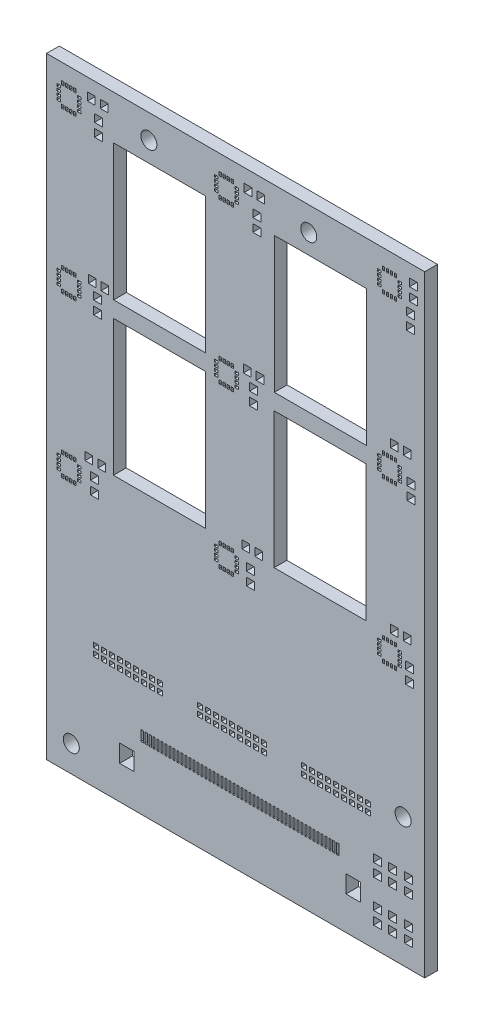
SolidWorks part; units mm, degrees
ref_plane "Plan de face" through (0, 0, 0) normal (0, 0, 1) x (1, 0, 0)
ref_plane "Plan de dessus" through (0, 0, 0) normal (0, 1, 0) x (1, 0, 0)
ref_plane "Plan de droite" through (0, 0, 0) normal (1, 0, 0) x (0, 0, -1)
sketch "Model" plane through (0, 0, 0) normal (0, 0, 1) x (1, 0, 0)
  line L0 (15.68, 10.185) -> (15.68, 10.775)
  line L1 (15.68, 10.775) -> (16.32, 10.775)
  line L2 (16.32, 10.775) -> (16.32, 10.185)
  line L3 (16.32, 10.185) -> (15.68, 10.185)
  line L4 (15.68, 9.225) -> (15.68, 9.815)
  line L5 (15.68, 9.815) -> (16.32, 9.815)
  line L6 (16.32, 9.815) -> (16.32, 9.225)
  line L7 (16.32, 9.225) -> (15.68, 9.225)
  line L8 (14.68, 10.185) -> (14.68, 10.775)
  line L9 (14.68, 10.775) -> (15.32, 10.775)
  line L10 (15.32, 10.775) -> (15.32, 10.185)
  line L11 (15.32, 10.185) -> (14.68, 10.185)
  line L12 (14.68, 9.225) -> (14.68, 9.815)
  line L13 (14.68, 9.815) -> (15.32, 9.815)
  line L14 (15.32, 9.815) -> (15.32, 9.225)
  line L15 (15.32, 9.225) -> (14.68, 9.225)
  line L16 (13.68, 10.185) -> (13.68, 10.775)
  line L17 (13.68, 10.775) -> (14.32, 10.775)
  line L18 (14.32, 10.775) -> (14.32, 10.185)
  line L19 (14.32, 10.185) -> (13.68, 10.185)
  line L20 (13.68, 9.225) -> (13.68, 9.815)
  line L21 (13.68, 9.815) -> (14.32, 9.815)
  line L22 (14.32, 9.815) -> (14.32, 9.225)
  line L23 (14.32, 9.225) -> (13.68, 9.225)
  line L24 (12.68, 10.185) -> (12.68, 10.775)
  line L25 (12.68, 10.775) -> (13.32, 10.775)
  line L26 (13.32, 10.775) -> (13.32, 10.185)
  line L27 (13.32, 10.185) -> (12.68, 10.185)
  line L28 (12.68, 9.225) -> (12.68, 9.815)
  line L29 (12.68, 9.815) -> (13.32, 9.815)
  line L30 (13.32, 9.815) -> (13.32, 9.225)
  line L31 (13.32, 9.225) -> (12.68, 9.225)
  line L32 (11.68, 10.185) -> (11.68, 10.775)
  line L33 (11.68, 10.775) -> (12.32, 10.775)
  line L34 (12.32, 10.775) -> (12.32, 10.185)
  line L35 (12.32, 10.185) -> (11.68, 10.185)
  line L36 (11.68, 9.225) -> (11.68, 9.815)
  line L37 (11.68, 9.815) -> (12.32, 9.815)
  line L38 (12.32, 9.815) -> (12.32, 9.225)
  line L39 (12.32, 9.225) -> (11.68, 9.225)
  line L40 (10.68, 10.185) -> (10.68, 10.775)
  line L41 (10.68, 10.775) -> (11.32, 10.775)
  line L42 (11.32, 10.775) -> (11.32, 10.185)
  line L43 (11.32, 10.185) -> (10.68, 10.185)
  line L44 (10.68, 9.225) -> (10.68, 9.815)
  line L45 (10.68, 9.815) -> (11.32, 9.815)
  line L46 (11.32, 9.815) -> (11.32, 9.225)
  line L47 (11.32, 9.225) -> (10.68, 9.225)
  line L48 (9.68, 10.185) -> (9.68, 10.775)
  line L49 (9.68, 10.775) -> (10.32, 10.775)
  line L50 (10.32, 10.775) -> (10.32, 10.185)
  line L51 (10.32, 10.185) -> (9.68, 10.185)
  line L52 (9.68, 9.225) -> (9.68, 9.815)
  line L53 (9.68, 9.815) -> (10.32, 9.815)
  line L54 (10.32, 9.815) -> (10.32, 9.225)
  line L55 (10.32, 9.225) -> (9.68, 9.225)
  line L56 (8.68, 10.185) -> (8.68, 10.775)
  line L57 (8.68, 10.775) -> (9.32, 10.775)
  line L58 (9.32, 10.775) -> (9.32, 10.185)
  line L59 (9.32, 10.185) -> (8.68, 10.185)
  line L60 (8.68, 9.225) -> (8.68, 9.815)
  line L61 (8.68, 9.815) -> (9.32, 9.815)
  line L62 (9.32, 9.815) -> (9.32, 9.225)
  line L63 (9.32, 9.225) -> (8.68, 9.225)
  line L64 (7.68, 10.185) -> (7.68, 10.775)
  line L65 (7.68, 10.775) -> (8.32, 10.775)
  line L66 (8.32, 10.775) -> (8.32, 10.185)
  line L67 (8.32, 10.185) -> (7.68, 10.185)
  line L68 (7.68, 9.225) -> (7.68, 9.815)
  line L69 (7.68, 9.815) -> (8.32, 9.815)
  line L70 (8.32, 9.815) -> (8.32, 9.225)
  line L71 (8.32, 9.225) -> (7.68, 9.225)
  line L72 (2.68, 10.185) -> (2.68, 10.775)
  line L73 (2.68, 10.775) -> (3.32, 10.775)
  line L74 (3.32, 10.775) -> (3.32, 10.185)
  line L75 (3.32, 10.185) -> (2.68, 10.185)
  line L76 (2.68, 9.225) -> (2.68, 9.815)
  line L77 (2.68, 9.815) -> (3.32, 9.815)
  line L78 (3.32, 9.815) -> (3.32, 9.225)
  line L79 (3.32, 9.225) -> (2.68, 9.225)
  line L80 (1.68, 10.185) -> (1.68, 10.775)
  line L81 (1.68, 10.775) -> (2.32, 10.775)
  line L82 (2.32, 10.775) -> (2.32, 10.185)
  line L83 (2.32, 10.185) -> (1.68, 10.185)
  line L84 (1.68, 9.225) -> (1.68, 9.815)
  line L85 (1.68, 9.815) -> (2.32, 9.815)
  line L86 (2.32, 9.815) -> (2.32, 9.225)
  line L87 (2.32, 9.225) -> (1.68, 9.225)
  line L88 (0.68, 10.185) -> (0.68, 10.775)
  line L89 (0.68, 10.775) -> (1.32, 10.775)
  line L90 (1.32, 10.775) -> (1.32, 10.185)
  line L91 (1.32, 10.185) -> (0.68, 10.185)
  line L92 (0.68, 9.225) -> (0.68, 9.815)
  line L93 (0.68, 9.815) -> (1.32, 9.815)
  line L94 (1.32, 9.815) -> (1.32, 9.225)
  line L95 (1.32, 9.225) -> (0.68, 9.225)
  line L96 (-0.32, 10.185) -> (-0.32, 10.775)
  line L97 (-0.32, 10.775) -> (0.32, 10.775)
  line L98 (0.32, 10.775) -> (0.32, 10.185)
  line L99 (0.32, 10.185) -> (-0.32, 10.185)
  line L100 (-0.32, 9.225) -> (-0.32, 9.815)
  line L101 (-0.32, 9.815) -> (0.32, 9.815)
  line L102 (0.32, 9.815) -> (0.32, 9.225)
  line L103 (0.32, 9.225) -> (-0.32, 9.225)
  line L104 (-1.32, 10.185) -> (-1.32, 10.775)
  line L105 (-1.32, 10.775) -> (-0.68, 10.775)
  line L106 (-0.68, 10.775) -> (-0.68, 10.185)
  line L107 (-0.68, 10.185) -> (-1.32, 10.185)
  line L108 (-1.32, 9.225) -> (-1.32, 9.815)
  line L109 (-1.32, 9.815) -> (-0.68, 9.815)
  line L110 (-0.68, 9.815) -> (-0.68, 9.225)
  line L111 (-0.68, 9.225) -> (-1.32, 9.225)
  line L112 (-2.32, 10.185) -> (-2.32, 10.775)
  line L113 (-2.32, 10.775) -> (-1.68, 10.775)
  line L114 (-1.68, 10.775) -> (-1.68, 10.185)
  line L115 (-1.68, 10.185) -> (-2.32, 10.185)
  line L116 (-2.32, 9.225) -> (-2.32, 9.815)
  line L117 (-2.32, 9.815) -> (-1.68, 9.815)
  line L118 (-1.68, 9.815) -> (-1.68, 9.225)
  line L119 (-1.68, 9.225) -> (-2.32, 9.225)
  line L120 (-3.32, 10.185) -> (-3.32, 10.775)
  line L121 (-3.32, 10.775) -> (-2.68, 10.775)
  line L122 (-2.68, 10.775) -> (-2.68, 10.185)
  line L123 (-2.68, 10.185) -> (-3.32, 10.185)
  line L124 (-3.32, 9.225) -> (-3.32, 9.815)
  line L125 (-3.32, 9.815) -> (-2.68, 9.815)
  line L126 (-2.68, 9.815) -> (-2.68, 9.225)
  line L127 (-2.68, 9.225) -> (-3.32, 9.225)
  line L128 (-4.32, 10.185) -> (-4.32, 10.775)
  line L129 (-4.32, 10.775) -> (-3.68, 10.775)
  line L130 (-3.68, 10.775) -> (-3.68, 10.185)
  line L131 (-3.68, 10.185) -> (-4.32, 10.185)
  line L132 (-4.32, 9.225) -> (-4.32, 9.815)
  line L133 (-4.32, 9.815) -> (-3.68, 9.815)
  line L134 (-3.68, 9.815) -> (-3.68, 9.225)
  line L135 (-3.68, 9.225) -> (-4.32, 9.225)
  line L136 (-5.32, 10.185) -> (-5.32, 10.775)
  line L137 (-5.32, 10.775) -> (-4.68, 10.775)
  line L138 (-4.68, 10.775) -> (-4.68, 10.185)
  line L139 (-4.68, 10.185) -> (-5.32, 10.185)
  line L140 (-5.32, 9.225) -> (-5.32, 9.815)
  line L141 (-5.32, 9.815) -> (-4.68, 9.815)
  line L142 (-4.68, 9.815) -> (-4.68, 9.225)
  line L143 (-4.68, 9.225) -> (-5.32, 9.225)
  line L144 (-10.32, 10.185) -> (-10.32, 10.775)
  line L145 (-10.32, 10.775) -> (-9.68, 10.775)
  line L146 (-9.68, 10.775) -> (-9.68, 10.185)
  line L147 (-9.68, 10.185) -> (-10.32, 10.185)
  line L148 (-10.32, 9.225) -> (-10.32, 9.815)
  line L149 (-10.32, 9.815) -> (-9.68, 9.815)
  line L150 (-9.68, 9.815) -> (-9.68, 9.225)
  line L151 (-9.68, 9.225) -> (-10.32, 9.225)
  line L152 (-11.32, 10.185) -> (-11.32, 10.775)
  line L153 (-11.32, 10.775) -> (-10.68, 10.775)
  line L154 (-10.68, 10.775) -> (-10.68, 10.185)
  line L155 (-10.68, 10.185) -> (-11.32, 10.185)
  line L156 (-11.32, 9.225) -> (-11.32, 9.815)
  line L157 (-11.32, 9.815) -> (-10.68, 9.815)
  line L158 (-10.68, 9.815) -> (-10.68, 9.225)
  line L159 (-10.68, 9.225) -> (-11.32, 9.225)
  line L160 (-12.32, 10.185) -> (-12.32, 10.775)
  line L161 (-12.32, 10.775) -> (-11.68, 10.775)
  line L162 (-11.68, 10.775) -> (-11.68, 10.185)
  line L163 (-11.68, 10.185) -> (-12.32, 10.185)
  line L164 (-12.32, 9.225) -> (-12.32, 9.815)
  line L165 (-12.32, 9.815) -> (-11.68, 9.815)
  line L166 (-11.68, 9.815) -> (-11.68, 9.225)
  line L167 (-11.68, 9.225) -> (-12.32, 9.225)
  line L168 (-13.32, 10.185) -> (-13.32, 10.775)
  line L169 (-13.32, 10.775) -> (-12.68, 10.775)
  line L170 (-12.68, 10.775) -> (-12.68, 10.185)
  line L171 (-12.68, 10.185) -> (-13.32, 10.185)
  line L172 (-13.32, 9.225) -> (-13.32, 9.815)
  line L173 (-13.32, 9.815) -> (-12.68, 9.815)
  line L174 (-12.68, 9.815) -> (-12.68, 9.225)
  line L175 (-12.68, 9.225) -> (-13.32, 9.225)
  line L176 (-14.32, 10.185) -> (-14.32, 10.775)
  line L177 (-14.32, 10.775) -> (-13.68, 10.775)
  line L178 (-13.68, 10.775) -> (-13.68, 10.185)
  line L179 (-13.68, 10.185) -> (-14.32, 10.185)
  line L180 (-14.32, 9.225) -> (-14.32, 9.815)
  line L181 (-14.32, 9.815) -> (-13.68, 9.815)
  line L182 (-13.68, 9.815) -> (-13.68, 9.225)
  line L183 (-13.68, 9.225) -> (-14.32, 9.225)
  line L184 (-15.32, 10.185) -> (-15.32, 10.775)
  line L185 (-15.32, 10.775) -> (-14.68, 10.775)
  line L186 (-14.68, 10.775) -> (-14.68, 10.185)
  line L187 (-14.68, 10.185) -> (-15.32, 10.185)
  line L188 (-15.32, 9.225) -> (-15.32, 9.815)
  line L189 (-15.32, 9.815) -> (-14.68, 9.815)
  line L190 (-14.68, 9.815) -> (-14.68, 9.225)
  line L191 (-14.68, 9.225) -> (-15.32, 9.225)
  line L192 (-16.32, 10.185) -> (-16.32, 10.775)
  line L193 (-16.32, 10.775) -> (-15.68, 10.775)
  line L194 (-15.68, 10.775) -> (-15.68, 10.185)
  line L195 (-15.68, 10.185) -> (-16.32, 10.185)
  line L196 (-16.32, 9.225) -> (-16.32, 9.815)
  line L197 (-16.32, 9.815) -> (-15.68, 9.815)
  line L198 (-15.68, 9.815) -> (-15.68, 9.225)
  line L199 (-15.68, 9.225) -> (-16.32, 9.225)
  line L200 (-17.32, 10.185) -> (-17.32, 10.775)
  line L201 (-17.32, 10.775) -> (-16.68, 10.775)
  line L202 (-16.68, 10.775) -> (-16.68, 10.185)
  line L203 (-16.68, 10.185) -> (-17.32, 10.185)
  line L204 (-17.32, 9.225) -> (-17.32, 9.815)
  line L205 (-17.32, 9.815) -> (-16.68, 9.815)
  line L206 (-16.68, 9.815) -> (-16.68, 9.225)
  line L207 (-16.68, 9.225) -> (-17.32, 9.225)
  line L208 (-18.32, 10.185) -> (-18.32, 10.775)
  line L209 (-18.32, 10.775) -> (-17.68, 10.775)
  line L210 (-17.68, 10.775) -> (-17.68, 10.185)
  line L211 (-17.68, 10.185) -> (-18.32, 10.185)
  line L212 (-18.32, 9.225) -> (-18.32, 9.815)
  line L213 (-18.32, 9.815) -> (-17.68, 9.815)
  line L214 (-17.68, 9.815) -> (-17.68, 9.225)
  line L215 (-17.68, 9.225) -> (-18.32, 9.225)
  line L216 (12.1, 2.975) -> (12.1, 4.275)
  line L217 (12.1, 4.275) -> (12.4, 4.275)
  line L218 (12.4, 4.275) -> (12.4, 2.975)
  line L219 (12.4, 2.975) -> (12.1, 2.975)
  line L220 (11.6, 2.975) -> (11.6, 4.275)
  line L221 (11.6, 4.275) -> (11.9, 4.275)
  line L222 (11.9, 4.275) -> (11.9, 2.975)
  line L223 (11.9, 2.975) -> (11.6, 2.975)
  line L224 (11.1, 2.975) -> (11.1, 4.275)
  line L225 (11.1, 4.275) -> (11.4, 4.275)
  line L226 (11.4, 4.275) -> (11.4, 2.975)
  line L227 (11.4, 2.975) -> (11.1, 2.975)
  line L228 (10.6, 2.975) -> (10.6, 4.275)
  line L229 (10.6, 4.275) -> (10.9, 4.275)
  line L230 (10.9, 4.275) -> (10.9, 2.975)
  line L231 (10.9, 2.975) -> (10.6, 2.975)
  line L232 (10.1, 2.975) -> (10.1, 4.275)
  line L233 (10.1, 4.275) -> (10.4, 4.275)
  line L234 (10.4, 4.275) -> (10.4, 2.975)
  line L235 (10.4, 2.975) -> (10.1, 2.975)
  line L236 (9.6, 2.975) -> (9.6, 4.275)
  line L237 (9.6, 4.275) -> (9.9, 4.275)
  line L238 (9.9, 4.275) -> (9.9, 2.975)
  line L239 (9.9, 2.975) -> (9.6, 2.975)
  line L240 (9.1, 2.975) -> (9.1, 4.275)
  line L241 (9.1, 4.275) -> (9.4, 4.275)
  line L242 (9.4, 4.275) -> (9.4, 2.975)
  line L243 (9.4, 2.975) -> (9.1, 2.975)
  line L244 (8.6, 2.975) -> (8.6, 4.275)
  line L245 (8.6, 4.275) -> (8.9, 4.275)
  line L246 (8.9, 4.275) -> (8.9, 2.975)
  line L247 (8.9, 2.975) -> (8.6, 2.975)
  line L248 (8.1, 2.975) -> (8.1, 4.275)
  line L249 (8.1, 4.275) -> (8.4, 4.275)
  line L250 (8.4, 4.275) -> (8.4, 2.975)
  line L251 (8.4, 2.975) -> (8.1, 2.975)
  line L252 (7.6, 2.975) -> (7.6, 4.275)
  line L253 (7.6, 4.275) -> (7.9, 4.275)
  line L254 (7.9, 4.275) -> (7.9, 2.975)
  line L255 (7.9, 2.975) -> (7.6, 2.975)
  line L256 (7.1, 2.975) -> (7.1, 4.275)
  line L257 (7.1, 4.275) -> (7.4, 4.275)
  line L258 (7.4, 4.275) -> (7.4, 2.975)
  line L259 (7.4, 2.975) -> (7.1, 2.975)
  line L260 (6.6, 2.975) -> (6.6, 4.275)
  line L261 (6.6, 4.275) -> (6.9, 4.275)
  line L262 (6.9, 4.275) -> (6.9, 2.975)
  line L263 (6.9, 2.975) -> (6.6, 2.975)
  line L264 (6.1, 2.975) -> (6.1, 4.275)
  line L265 (6.1, 4.275) -> (6.4, 4.275)
  line L266 (6.4, 4.275) -> (6.4, 2.975)
  line L267 (6.4, 2.975) -> (6.1, 2.975)
  line L268 (5.6, 2.975) -> (5.6, 4.275)
  line L269 (5.6, 4.275) -> (5.9, 4.275)
  line L270 (5.9, 4.275) -> (5.9, 2.975)
  line L271 (5.9, 2.975) -> (5.6, 2.975)
  line L272 (5.1, 2.975) -> (5.1, 4.275)
  line L273 (5.1, 4.275) -> (5.4, 4.275)
  line L274 (5.4, 4.275) -> (5.4, 2.975)
  line L275 (5.4, 2.975) -> (5.1, 2.975)
  line L276 (4.6, 2.975) -> (4.6, 4.275)
  line L277 (4.6, 4.275) -> (4.9, 4.275)
  line L278 (4.9, 4.275) -> (4.9, 2.975)
  line L279 (4.9, 2.975) -> (4.6, 2.975)
  line L280 (4.1, 2.975) -> (4.1, 4.275)
  line L281 (4.1, 4.275) -> (4.4, 4.275)
  line L282 (4.4, 4.275) -> (4.4, 2.975)
  line L283 (4.4, 2.975) -> (4.1, 2.975)
  line L284 (3.6, 2.975) -> (3.6, 4.275)
  line L285 (3.6, 4.275) -> (3.9, 4.275)
  line L286 (3.9, 4.275) -> (3.9, 2.975)
  line L287 (3.9, 2.975) -> (3.6, 2.975)
  line L288 (3.1, 2.975) -> (3.1, 4.275)
  line L289 (3.1, 4.275) -> (3.4, 4.275)
  line L290 (3.4, 4.275) -> (3.4, 2.975)
  line L291 (3.4, 2.975) -> (3.1, 2.975)
  line L292 (2.6, 2.975) -> (2.6, 4.275)
  line L293 (2.6, 4.275) -> (2.9, 4.275)
  line L294 (2.9, 4.275) -> (2.9, 2.975)
  line L295 (2.9, 2.975) -> (2.6, 2.975)
  line L296 (2.1, 2.975) -> (2.1, 4.275)
  line L297 (2.1, 4.275) -> (2.4, 4.275)
  line L298 (2.4, 4.275) -> (2.4, 2.975)
  line L299 (2.4, 2.975) -> (2.1, 2.975)
  line L300 (1.6, 2.975) -> (1.6, 4.275)
  line L301 (1.6, 4.275) -> (1.9, 4.275)
  line L302 (1.9, 4.275) -> (1.9, 2.975)
  line L303 (1.9, 2.975) -> (1.6, 2.975)
  line L304 (1.1, 2.975) -> (1.1, 4.275)
  line L305 (1.1, 4.275) -> (1.4, 4.275)
  line L306 (1.4, 4.275) -> (1.4, 2.975)
  line L307 (1.4, 2.975) -> (1.1, 2.975)
  line L308 (0.6, 2.975) -> (0.6, 4.275)
  line L309 (0.6, 4.275) -> (0.9, 4.275)
  line L310 (0.9, 4.275) -> (0.9, 2.975)
  line L311 (0.9, 2.975) -> (0.6, 2.975)
  line L312 (0.1, 2.975) -> (0.1, 4.275)
  line L313 (0.1, 4.275) -> (0.4, 4.275)
  line L314 (0.4, 4.275) -> (0.4, 2.975)
  line L315 (0.4, 2.975) -> (0.1, 2.975)
  line L316 (-0.4, 2.975) -> (-0.4, 4.275)
  line L317 (-0.4, 4.275) -> (-0.1, 4.275)
  line L318 (-0.1, 4.275) -> (-0.1, 2.975)
  line L319 (-0.1, 2.975) -> (-0.4, 2.975)
  line L320 (-0.9, 2.975) -> (-0.9, 4.275)
  line L321 (-0.9, 4.275) -> (-0.6, 4.275)
  line L322 (-0.6, 4.275) -> (-0.6, 2.975)
  line L323 (-0.6, 2.975) -> (-0.9, 2.975)
  line L324 (-1.4, 2.975) -> (-1.4, 4.275)
  line L325 (-1.4, 4.275) -> (-1.1, 4.275)
  line L326 (-1.1, 4.275) -> (-1.1, 2.975)
  line L327 (-1.1, 2.975) -> (-1.4, 2.975)
  line L328 (-1.9, 2.975) -> (-1.9, 4.275)
  line L329 (-1.9, 4.275) -> (-1.6, 4.275)
  line L330 (-1.6, 4.275) -> (-1.6, 2.975)
  line L331 (-1.6, 2.975) -> (-1.9, 2.975)
  line L332 (-2.4, 2.975) -> (-2.4, 4.275)
  line L333 (-2.4, 4.275) -> (-2.1, 4.275)
  line L334 (-2.1, 4.275) -> (-2.1, 2.975)
  line L335 (-2.1, 2.975) -> (-2.4, 2.975)
  line L336 (-2.9, 2.975) -> (-2.9, 4.275)
  line L337 (-2.9, 4.275) -> (-2.6, 4.275)
  line L338 (-2.6, 4.275) -> (-2.6, 2.975)
  line L339 (-2.6, 2.975) -> (-2.9, 2.975)
  line L340 (-3.4, 2.975) -> (-3.4, 4.275)
  line L341 (-3.4, 4.275) -> (-3.1, 4.275)
  line L342 (-3.1, 4.275) -> (-3.1, 2.975)
  line L343 (-3.1, 2.975) -> (-3.4, 2.975)
  line L344 (-3.9, 2.975) -> (-3.9, 4.275)
  line L345 (-3.9, 4.275) -> (-3.6, 4.275)
  line L346 (-3.6, 4.275) -> (-3.6, 2.975)
  line L347 (-3.6, 2.975) -> (-3.9, 2.975)
  line L348 (-4.4, 2.975) -> (-4.4, 4.275)
  line L349 (-4.4, 4.275) -> (-4.1, 4.275)
  line L350 (-4.1, 4.275) -> (-4.1, 2.975)
  line L351 (-4.1, 2.975) -> (-4.4, 2.975)
  line L352 (-4.9, 2.975) -> (-4.9, 4.275)
  line L353 (-4.9, 4.275) -> (-4.6, 4.275)
  line L354 (-4.6, 4.275) -> (-4.6, 2.975)
  line L355 (-4.6, 2.975) -> (-4.9, 2.975)
  line L356 (-5.4, 2.975) -> (-5.4, 4.275)
  line L357 (-5.4, 4.275) -> (-5.1, 4.275)
  line L358 (-5.1, 4.275) -> (-5.1, 2.975)
  line L359 (-5.1, 2.975) -> (-5.4, 2.975)
  line L360 (-5.9, 2.975) -> (-5.9, 4.275)
  line L361 (-5.9, 4.275) -> (-5.6, 4.275)
  line L362 (-5.6, 4.275) -> (-5.6, 2.975)
  line L363 (-5.6, 2.975) -> (-5.9, 2.975)
  line L364 (-6.4, 2.975) -> (-6.4, 4.275)
  line L365 (-6.4, 4.275) -> (-6.1, 4.275)
  line L366 (-6.1, 4.275) -> (-6.1, 2.975)
  line L367 (-6.1, 2.975) -> (-6.4, 2.975)
  line L368 (-6.9, 2.975) -> (-6.9, 4.275)
  line L369 (-6.9, 4.275) -> (-6.6, 4.275)
  line L370 (-6.6, 4.275) -> (-6.6, 2.975)
  line L371 (-6.6, 2.975) -> (-6.9, 2.975)
  line L372 (-7.4, 2.975) -> (-7.4, 4.275)
  line L373 (-7.4, 4.275) -> (-7.1, 4.275)
  line L374 (-7.1, 4.275) -> (-7.1, 2.975)
  line L375 (-7.1, 2.975) -> (-7.4, 2.975)
  line L376 (-7.9, 2.975) -> (-7.9, 4.275)
  line L377 (-7.9, 4.275) -> (-7.6, 4.275)
  line L378 (-7.6, 4.275) -> (-7.6, 2.975)
  line L379 (-7.6, 2.975) -> (-7.9, 2.975)
  line L380 (-8.4, 2.975) -> (-8.4, 4.275)
  line L381 (-8.4, 4.275) -> (-8.1, 4.275)
  line L382 (-8.1, 4.275) -> (-8.1, 2.975)
  line L383 (-8.1, 2.975) -> (-8.4, 2.975)
  line L384 (-8.9, 2.975) -> (-8.9, 4.275)
  line L385 (-8.9, 4.275) -> (-8.6, 4.275)
  line L386 (-8.6, 4.275) -> (-8.6, 2.975)
  line L387 (-8.6, 2.975) -> (-8.9, 2.975)
  line L388 (-9.4, 2.975) -> (-9.4, 4.275)
  line L389 (-9.4, 4.275) -> (-9.1, 4.275)
  line L390 (-9.1, 4.275) -> (-9.1, 2.975)
  line L391 (-9.1, 2.975) -> (-9.4, 2.975)
  line L392 (-9.9, 2.975) -> (-9.9, 4.275)
  line L393 (-9.9, 4.275) -> (-9.6, 4.275)
  line L394 (-9.6, 4.275) -> (-9.6, 2.975)
  line L395 (-9.6, 2.975) -> (-9.9, 2.975)
  line L396 (-10.4, 2.975) -> (-10.4, 4.275)
  line L397 (-10.4, 4.275) -> (-10.1, 4.275)
  line L398 (-10.1, 4.275) -> (-10.1, 2.975)
  line L399 (-10.1, 2.975) -> (-10.4, 2.975)
  line L400 (-10.9, 2.975) -> (-10.9, 4.275)
  line L401 (-10.9, 4.275) -> (-10.6, 4.275)
  line L402 (-10.6, 4.275) -> (-10.6, 2.975)
  line L403 (-10.6, 2.975) -> (-10.9, 2.975)
  line L404 (-11.4, 2.975) -> (-11.4, 4.275)
  line L405 (-11.4, 4.275) -> (-11.1, 4.275)
  line L406 (-11.1, 4.275) -> (-11.1, 2.975)
  line L407 (-11.1, 2.975) -> (-11.4, 2.975)
  line L408 (-11.9, 2.975) -> (-11.9, 4.275)
  line L409 (-11.9, 4.275) -> (-11.6, 4.275)
  line L410 (-11.6, 4.275) -> (-11.6, 2.975)
  line L411 (-11.6, 2.975) -> (-11.9, 2.975)
  line L412 (-12.4, 2.975) -> (-12.4, 4.275)
  line L413 (-12.4, 4.275) -> (-12.1, 4.275)
  line L414 (-12.1, 4.275) -> (-12.1, 2.975)
  line L415 (-12.1, 2.975) -> (-12.4, 2.975)
  line L416 (13.25, -0.725) -> (13.25, 1.475)
  line L417 (13.25, 1.475) -> (15.05, 1.475)
  line L418 (15.05, 1.475) -> (15.05, -0.725)
  line L419 (15.05, -0.725) -> (13.25, -0.725)
  line L420 (-15.05, -0.725) -> (-15.05, 1.475)
  line L421 (-15.05, 1.475) -> (-13.25, 1.475)
  line L422 (-13.25, 1.475) -> (-13.25, -0.725)
  line L423 (-13.25, -0.725) -> (-15.05, -0.725)
  line L424 (17.2, 28.7) -> (17.2, 29)
  line L425 (17.2, 29) -> (17.65, 29)
  line L426 (17.65, 29) -> (17.65, 28.7)
  line L427 (17.65, 28.7) -> (17.2, 28.7)
  line L428 (19.75, 27.7) -> (19.75, 28)
  line L429 (19.75, 28) -> (20.2, 28)
  line L430 (20.2, 28) -> (20.2, 27.7)
  line L431 (20.2, 27.7) -> (19.75, 27.7)
  line L432 (19.75, 28.2) -> (19.75, 28.5)
  line L433 (19.75, 28.5) -> (20.2, 28.5)
  line L434 (20.2, 28.5) -> (20.2, 28.2)
  line L435 (20.2, 28.2) -> (19.75, 28.2)
  line L436 (19.75, 28.7) -> (19.75, 29)
  line L437 (19.75, 29) -> (20.2, 29)
  line L438 (20.2, 29) -> (20.2, 28.7)
  line L439 (20.2, 28.7) -> (19.75, 28.7)
  line L440 (19.3, 29.15) -> (19.3, 29.6)
  line L441 (19.3, 29.6) -> (19.6, 29.6)
  line L442 (19.6, 29.6) -> (19.6, 29.15)
  line L443 (19.6, 29.15) -> (19.3, 29.15)
  line L444 (18.8, 29.15) -> (18.8, 29.6)
  line L445 (18.8, 29.6) -> (19.1, 29.6)
  line L446 (19.1, 29.6) -> (19.1, 29.15)
  line L447 (19.1, 29.15) -> (18.8, 29.15)
  line L448 (18.3, 29.15) -> (18.3, 29.6)
  line L449 (18.3, 29.6) -> (18.6, 29.6)
  line L450 (18.6, 29.6) -> (18.6, 29.15)
  line L451 (18.6, 29.15) -> (18.3, 29.15)
  line L452 (17.8, 29.15) -> (17.8, 29.6)
  line L453 (17.8, 29.6) -> (18.1, 29.6)
  line L454 (18.1, 29.6) -> (18.1, 29.15)
  line L455 (18.1, 29.15) -> (17.8, 29.15)
  line L456 (17.2, 28.2) -> (17.2, 28.5)
  line L457 (17.2, 28.5) -> (17.65, 28.5)
  line L458 (17.65, 28.5) -> (17.65, 28.2)
  line L459 (17.65, 28.2) -> (17.2, 28.2)
  line L460 (17.2, 27.7) -> (17.2, 28)
  line L461 (17.2, 28) -> (17.65, 28)
  line L462 (17.65, 28) -> (17.65, 27.7)
  line L463 (17.65, 27.7) -> (17.2, 27.7)
  line L464 (17.2, 27.2) -> (17.2, 27.5)
  line L465 (17.2, 27.5) -> (17.65, 27.5)
  line L466 (17.65, 27.5) -> (17.65, 27.2)
  line L467 (17.65, 27.2) -> (17.2, 27.2)
  line L468 (17.8, 26.6) -> (17.8, 27.05)
  line L469 (17.8, 27.05) -> (18.1, 27.05)
  line L470 (18.1, 27.05) -> (18.1, 26.6)
  line L471 (18.1, 26.6) -> (17.8, 26.6)
  line L472 (18.3, 26.6) -> (18.3, 27.05)
  line L473 (18.3, 27.05) -> (18.6, 27.05)
  line L474 (18.6, 27.05) -> (18.6, 26.6)
  line L475 (18.6, 26.6) -> (18.3, 26.6)
  line L476 (18.8, 26.6) -> (18.8, 27.05)
  line L477 (18.8, 27.05) -> (19.1, 27.05)
  line L478 (19.1, 27.05) -> (19.1, 26.6)
  line L479 (19.1, 26.6) -> (18.8, 26.6)
  line L480 (19.3, 26.6) -> (19.3, 27.05)
  line L481 (19.3, 27.05) -> (19.6, 27.05)
  line L482 (19.6, 27.05) -> (19.6, 26.6)
  line L483 (19.6, 26.6) -> (19.3, 26.6)
  line L484 (19.75, 27.2) -> (19.75, 27.5)
  line L485 (19.75, 27.5) -> (20.2, 27.5)
  line L486 (20.2, 27.5) -> (20.2, 27.2)
  line L487 (20.2, 27.2) -> (19.75, 27.2)
  line L488 (-3.2, 28.7) -> (-3.2, 29)
  line L489 (-3.2, 29) -> (-2.75, 29)
  line L490 (-2.75, 29) -> (-2.75, 28.7)
  line L491 (-2.75, 28.7) -> (-3.2, 28.7)
  line L492 (-0.65, 27.7) -> (-0.65, 28)
  line L493 (-0.65, 28) -> (-0.2, 28)
  line L494 (-0.2, 28) -> (-0.2, 27.7)
  line L495 (-0.2, 27.7) -> (-0.65, 27.7)
  line L496 (-0.65, 28.2) -> (-0.65, 28.5)
  line L497 (-0.65, 28.5) -> (-0.2, 28.5)
  line L498 (-0.2, 28.5) -> (-0.2, 28.2)
  line L499 (-0.2, 28.2) -> (-0.65, 28.2)
  line L500 (-0.65, 28.7) -> (-0.65, 29)
  line L501 (-0.65, 29) -> (-0.2, 29)
  line L502 (-0.2, 29) -> (-0.2, 28.7)
  line L503 (-0.2, 28.7) -> (-0.65, 28.7)
  line L504 (-1.1, 29.15) -> (-1.1, 29.6)
  line L505 (-1.1, 29.6) -> (-0.8, 29.6)
  line L506 (-0.8, 29.6) -> (-0.8, 29.15)
  line L507 (-0.8, 29.15) -> (-1.1, 29.15)
  line L508 (-1.6, 29.15) -> (-1.6, 29.6)
  line L509 (-1.6, 29.6) -> (-1.3, 29.6)
  line L510 (-1.3, 29.6) -> (-1.3, 29.15)
  line L511 (-1.3, 29.15) -> (-1.6, 29.15)
  line L512 (-2.1, 29.15) -> (-2.1, 29.6)
  line L513 (-2.1, 29.6) -> (-1.8, 29.6)
  line L514 (-1.8, 29.6) -> (-1.8, 29.15)
  line L515 (-1.8, 29.15) -> (-2.1, 29.15)
  line L516 (-2.6, 29.15) -> (-2.6, 29.6)
  line L517 (-2.6, 29.6) -> (-2.3, 29.6)
  line L518 (-2.3, 29.6) -> (-2.3, 29.15)
  line L519 (-2.3, 29.15) -> (-2.6, 29.15)
  line L520 (-3.2, 28.2) -> (-3.2, 28.5)
  line L521 (-3.2, 28.5) -> (-2.75, 28.5)
  line L522 (-2.75, 28.5) -> (-2.75, 28.2)
  line L523 (-2.75, 28.2) -> (-3.2, 28.2)
  line L524 (-3.2, 27.7) -> (-3.2, 28)
  line L525 (-3.2, 28) -> (-2.75, 28)
  line L526 (-2.75, 28) -> (-2.75, 27.7)
  line L527 (-2.75, 27.7) -> (-3.2, 27.7)
  line L528 (-3.2, 27.2) -> (-3.2, 27.5)
  line L529 (-3.2, 27.5) -> (-2.75, 27.5)
  line L530 (-2.75, 27.5) -> (-2.75, 27.2)
  line L531 (-2.75, 27.2) -> (-3.2, 27.2)
  line L532 (-2.6, 26.6) -> (-2.6, 27.05)
  line L533 (-2.6, 27.05) -> (-2.3, 27.05)
  line L534 (-2.3, 27.05) -> (-2.3, 26.6)
  line L535 (-2.3, 26.6) -> (-2.6, 26.6)
  line L536 (-2.1, 26.6) -> (-2.1, 27.05)
  line L537 (-2.1, 27.05) -> (-1.8, 27.05)
  line L538 (-1.8, 27.05) -> (-1.8, 26.6)
  line L539 (-1.8, 26.6) -> (-2.1, 26.6)
  line L540 (-1.6, 26.6) -> (-1.6, 27.05)
  line L541 (-1.6, 27.05) -> (-1.3, 27.05)
  line L542 (-1.3, 27.05) -> (-1.3, 26.6)
  line L543 (-1.3, 26.6) -> (-1.6, 26.6)
  line L544 (-1.1, 26.6) -> (-1.1, 27.05)
  line L545 (-1.1, 27.05) -> (-0.8, 27.05)
  line L546 (-0.8, 27.05) -> (-0.8, 26.6)
  line L547 (-0.8, 26.6) -> (-1.1, 26.6)
  line L548 (-0.65, 27.2) -> (-0.65, 27.5)
  line L549 (-0.65, 27.5) -> (-0.2, 27.5)
  line L550 (-0.2, 27.5) -> (-0.2, 27.2)
  line L551 (-0.2, 27.2) -> (-0.65, 27.2)
  line L552 (-22.9, 28.7) -> (-22.9, 29)
  line L553 (-22.9, 29) -> (-22.45, 29)
  line L554 (-22.45, 29) -> (-22.45, 28.7)
  line L555 (-22.45, 28.7) -> (-22.9, 28.7)
  line L556 (-20.35, 27.7) -> (-20.35, 28)
  line L557 (-20.35, 28) -> (-19.9, 28)
  line L558 (-19.9, 28) -> (-19.9, 27.7)
  line L559 (-19.9, 27.7) -> (-20.35, 27.7)
  line L560 (-20.35, 28.2) -> (-20.35, 28.5)
  line L561 (-20.35, 28.5) -> (-19.9, 28.5)
  line L562 (-19.9, 28.5) -> (-19.9, 28.2)
  line L563 (-19.9, 28.2) -> (-20.35, 28.2)
  line L564 (-20.35, 28.7) -> (-20.35, 29)
  line L565 (-20.35, 29) -> (-19.9, 29)
  line L566 (-19.9, 29) -> (-19.9, 28.7)
  line L567 (-19.9, 28.7) -> (-20.35, 28.7)
  line L568 (-20.8, 29.15) -> (-20.8, 29.6)
  line L569 (-20.8, 29.6) -> (-20.5, 29.6)
  line L570 (-20.5, 29.6) -> (-20.5, 29.15)
  line L571 (-20.5, 29.15) -> (-20.8, 29.15)
  line L572 (-21.3, 29.15) -> (-21.3, 29.6)
  line L573 (-21.3, 29.6) -> (-21, 29.6)
  line L574 (-21, 29.6) -> (-21, 29.15)
  line L575 (-21, 29.15) -> (-21.3, 29.15)
  line L576 (-21.8, 29.15) -> (-21.8, 29.6)
  line L577 (-21.8, 29.6) -> (-21.5, 29.6)
  line L578 (-21.5, 29.6) -> (-21.5, 29.15)
  line L579 (-21.5, 29.15) -> (-21.8, 29.15)
  line L580 (-22.3, 29.15) -> (-22.3, 29.6)
  line L581 (-22.3, 29.6) -> (-22, 29.6)
  line L582 (-22, 29.6) -> (-22, 29.15)
  line L583 (-22, 29.15) -> (-22.3, 29.15)
  line L584 (-22.9, 28.2) -> (-22.9, 28.5)
  line L585 (-22.9, 28.5) -> (-22.45, 28.5)
  line L586 (-22.45, 28.5) -> (-22.45, 28.2)
  line L587 (-22.45, 28.2) -> (-22.9, 28.2)
  line L588 (-22.9, 27.7) -> (-22.9, 28)
  line L589 (-22.9, 28) -> (-22.45, 28)
  line L590 (-22.45, 28) -> (-22.45, 27.7)
  line L591 (-22.45, 27.7) -> (-22.9, 27.7)
  line L592 (-22.9, 27.2) -> (-22.9, 27.5)
  line L593 (-22.9, 27.5) -> (-22.45, 27.5)
  line L594 (-22.45, 27.5) -> (-22.45, 27.2)
  line L595 (-22.45, 27.2) -> (-22.9, 27.2)
  line L596 (-22.3, 26.6) -> (-22.3, 27.05)
  line L597 (-22.3, 27.05) -> (-22, 27.05)
  line L598 (-22, 27.05) -> (-22, 26.6)
  line L599 (-22, 26.6) -> (-22.3, 26.6)
  line L600 (-21.8, 26.6) -> (-21.8, 27.05)
  line L601 (-21.8, 27.05) -> (-21.5, 27.05)
  line L602 (-21.5, 27.05) -> (-21.5, 26.6)
  line L603 (-21.5, 26.6) -> (-21.8, 26.6)
  line L604 (-21.3, 26.6) -> (-21.3, 27.05)
  line L605 (-21.3, 27.05) -> (-21, 27.05)
  line L606 (-21, 27.05) -> (-21, 26.6)
  line L607 (-21, 26.6) -> (-21.3, 26.6)
  line L608 (-20.8, 26.6) -> (-20.8, 27.05)
  line L609 (-20.8, 27.05) -> (-20.5, 27.05)
  line L610 (-20.5, 27.05) -> (-20.5, 26.6)
  line L611 (-20.5, 26.6) -> (-20.8, 26.6)
  line L612 (-20.35, 27.2) -> (-20.35, 27.5)
  line L613 (-20.35, 27.5) -> (-19.9, 27.5)
  line L614 (-19.9, 27.5) -> (-19.9, 27.2)
  line L615 (-19.9, 27.2) -> (-20.35, 27.2)
  line L616 (17.2, 68.7) -> (17.2, 69)
  line L617 (17.2, 69) -> (17.65, 69)
  line L618 (17.65, 69) -> (17.65, 68.7)
  line L619 (17.65, 68.7) -> (17.2, 68.7)
  line L620 (19.75, 67.7) -> (19.75, 68)
  line L621 (19.75, 68) -> (20.2, 68)
  line L622 (20.2, 68) -> (20.2, 67.7)
  line L623 (20.2, 67.7) -> (19.75, 67.7)
  line L624 (19.75, 68.2) -> (19.75, 68.5)
  line L625 (19.75, 68.5) -> (20.2, 68.5)
  line L626 (20.2, 68.5) -> (20.2, 68.2)
  line L627 (20.2, 68.2) -> (19.75, 68.2)
  line L628 (19.75, 68.7) -> (19.75, 69)
  line L629 (19.75, 69) -> (20.2, 69)
  line L630 (20.2, 69) -> (20.2, 68.7)
  line L631 (20.2, 68.7) -> (19.75, 68.7)
  line L632 (19.3, 69.15) -> (19.3, 69.6)
  line L633 (19.3, 69.6) -> (19.6, 69.6)
  line L634 (19.6, 69.6) -> (19.6, 69.15)
  line L635 (19.6, 69.15) -> (19.3, 69.15)
  line L636 (18.8, 69.15) -> (18.8, 69.6)
  line L637 (18.8, 69.6) -> (19.1, 69.6)
  line L638 (19.1, 69.6) -> (19.1, 69.15)
  line L639 (19.1, 69.15) -> (18.8, 69.15)
  line L640 (18.3, 69.15) -> (18.3, 69.6)
  line L641 (18.3, 69.6) -> (18.6, 69.6)
  line L642 (18.6, 69.6) -> (18.6, 69.15)
  line L643 (18.6, 69.15) -> (18.3, 69.15)
  line L644 (17.8, 69.15) -> (17.8, 69.6)
  line L645 (17.8, 69.6) -> (18.1, 69.6)
  line L646 (18.1, 69.6) -> (18.1, 69.15)
  line L647 (18.1, 69.15) -> (17.8, 69.15)
  line L648 (17.2, 68.2) -> (17.2, 68.5)
  line L649 (17.2, 68.5) -> (17.65, 68.5)
  line L650 (17.65, 68.5) -> (17.65, 68.2)
  line L651 (17.65, 68.2) -> (17.2, 68.2)
  line L652 (17.2, 67.7) -> (17.2, 68)
  line L653 (17.2, 68) -> (17.65, 68)
  line L654 (17.65, 68) -> (17.65, 67.7)
  line L655 (17.65, 67.7) -> (17.2, 67.7)
  line L656 (17.2, 67.2) -> (17.2, 67.5)
  line L657 (17.2, 67.5) -> (17.65, 67.5)
  line L658 (17.65, 67.5) -> (17.65, 67.2)
  line L659 (17.65, 67.2) -> (17.2, 67.2)
  line L660 (17.8, 66.6) -> (17.8, 67.05)
  line L661 (17.8, 67.05) -> (18.1, 67.05)
  line L662 (18.1, 67.05) -> (18.1, 66.6)
  line L663 (18.1, 66.6) -> (17.8, 66.6)
  line L664 (18.3, 66.6) -> (18.3, 67.05)
  line L665 (18.3, 67.05) -> (18.6, 67.05)
  line L666 (18.6, 67.05) -> (18.6, 66.6)
  line L667 (18.6, 66.6) -> (18.3, 66.6)
  line L668 (18.8, 66.6) -> (18.8, 67.05)
  line L669 (18.8, 67.05) -> (19.1, 67.05)
  line L670 (19.1, 67.05) -> (19.1, 66.6)
  line L671 (19.1, 66.6) -> (18.8, 66.6)
  line L672 (19.3, 66.6) -> (19.3, 67.05)
  line L673 (19.3, 67.05) -> (19.6, 67.05)
  line L674 (19.6, 67.05) -> (19.6, 66.6)
  line L675 (19.6, 66.6) -> (19.3, 66.6)
  line L676 (19.75, 67.2) -> (19.75, 67.5)
  line L677 (19.75, 67.5) -> (20.2, 67.5)
  line L678 (20.2, 67.5) -> (20.2, 67.2)
  line L679 (20.2, 67.2) -> (19.75, 67.2)
  line L680 (-3.2, 68.7) -> (-3.2, 69)
  line L681 (-3.2, 69) -> (-2.75, 69)
  line L682 (-2.75, 69) -> (-2.75, 68.7)
  line L683 (-2.75, 68.7) -> (-3.2, 68.7)
  line L684 (-0.65, 67.7) -> (-0.65, 68)
  line L685 (-0.65, 68) -> (-0.2, 68)
  line L686 (-0.2, 68) -> (-0.2, 67.7)
  line L687 (-0.2, 67.7) -> (-0.65, 67.7)
  line L688 (-0.65, 68.2) -> (-0.65, 68.5)
  line L689 (-0.65, 68.5) -> (-0.2, 68.5)
  line L690 (-0.2, 68.5) -> (-0.2, 68.2)
  line L691 (-0.2, 68.2) -> (-0.65, 68.2)
  line L692 (-0.65, 68.7) -> (-0.65, 69)
  line L693 (-0.65, 69) -> (-0.2, 69)
  line L694 (-0.2, 69) -> (-0.2, 68.7)
  line L695 (-0.2, 68.7) -> (-0.65, 68.7)
  line L696 (-1.1, 69.15) -> (-1.1, 69.6)
  line L697 (-1.1, 69.6) -> (-0.8, 69.6)
  line L698 (-0.8, 69.6) -> (-0.8, 69.15)
  line L699 (-0.8, 69.15) -> (-1.1, 69.15)
  line L700 (-1.6, 69.15) -> (-1.6, 69.6)
  line L701 (-1.6, 69.6) -> (-1.3, 69.6)
  line L702 (-1.3, 69.6) -> (-1.3, 69.15)
  line L703 (-1.3, 69.15) -> (-1.6, 69.15)
  line L704 (-2.1, 69.15) -> (-2.1, 69.6)
  line L705 (-2.1, 69.6) -> (-1.8, 69.6)
  line L706 (-1.8, 69.6) -> (-1.8, 69.15)
  line L707 (-1.8, 69.15) -> (-2.1, 69.15)
  line L708 (-2.6, 69.15) -> (-2.6, 69.6)
  line L709 (-2.6, 69.6) -> (-2.3, 69.6)
  line L710 (-2.3, 69.6) -> (-2.3, 69.15)
  line L711 (-2.3, 69.15) -> (-2.6, 69.15)
  line L712 (-3.2, 68.2) -> (-3.2, 68.5)
  line L713 (-3.2, 68.5) -> (-2.75, 68.5)
  line L714 (-2.75, 68.5) -> (-2.75, 68.2)
  line L715 (-2.75, 68.2) -> (-3.2, 68.2)
  line L716 (-3.2, 67.7) -> (-3.2, 68)
  line L717 (-3.2, 68) -> (-2.75, 68)
  line L718 (-2.75, 68) -> (-2.75, 67.7)
  line L719 (-2.75, 67.7) -> (-3.2, 67.7)
  line L720 (-3.2, 67.2) -> (-3.2, 67.5)
  line L721 (-3.2, 67.5) -> (-2.75, 67.5)
  line L722 (-2.75, 67.5) -> (-2.75, 67.2)
  line L723 (-2.75, 67.2) -> (-3.2, 67.2)
  line L724 (-2.6, 66.6) -> (-2.6, 67.05)
  line L725 (-2.6, 67.05) -> (-2.3, 67.05)
  line L726 (-2.3, 67.05) -> (-2.3, 66.6)
  line L727 (-2.3, 66.6) -> (-2.6, 66.6)
  line L728 (-2.1, 66.6) -> (-2.1, 67.05)
  line L729 (-2.1, 67.05) -> (-1.8, 67.05)
  line L730 (-1.8, 67.05) -> (-1.8, 66.6)
  line L731 (-1.8, 66.6) -> (-2.1, 66.6)
  line L732 (-1.6, 66.6) -> (-1.6, 67.05)
  line L733 (-1.6, 67.05) -> (-1.3, 67.05)
  line L734 (-1.3, 67.05) -> (-1.3, 66.6)
  line L735 (-1.3, 66.6) -> (-1.6, 66.6)
  line L736 (-1.1, 66.6) -> (-1.1, 67.05)
  line L737 (-1.1, 67.05) -> (-0.8, 67.05)
  line L738 (-0.8, 67.05) -> (-0.8, 66.6)
  line L739 (-0.8, 66.6) -> (-1.1, 66.6)
  line L740 (-0.65, 67.2) -> (-0.65, 67.5)
  line L741 (-0.65, 67.5) -> (-0.2, 67.5)
  line L742 (-0.2, 67.5) -> (-0.2, 67.2)
  line L743 (-0.2, 67.2) -> (-0.65, 67.2)
  line L744 (-22.9, 68.7) -> (-22.9, 69)
  line L745 (-22.9, 69) -> (-22.45, 69)
  line L746 (-22.45, 69) -> (-22.45, 68.7)
  line L747 (-22.45, 68.7) -> (-22.9, 68.7)
  line L748 (-20.35, 67.7) -> (-20.35, 68)
  line L749 (-20.35, 68) -> (-19.9, 68)
  line L750 (-19.9, 68) -> (-19.9, 67.7)
  line L751 (-19.9, 67.7) -> (-20.35, 67.7)
  line L752 (-20.35, 68.2) -> (-20.35, 68.5)
  line L753 (-20.35, 68.5) -> (-19.9, 68.5)
  line L754 (-19.9, 68.5) -> (-19.9, 68.2)
  line L755 (-19.9, 68.2) -> (-20.35, 68.2)
  line L756 (-20.35, 68.7) -> (-20.35, 69)
  line L757 (-20.35, 69) -> (-19.9, 69)
  line L758 (-19.9, 69) -> (-19.9, 68.7)
  line L759 (-19.9, 68.7) -> (-20.35, 68.7)
  line L760 (-20.8, 69.15) -> (-20.8, 69.6)
  line L761 (-20.8, 69.6) -> (-20.5, 69.6)
  line L762 (-20.5, 69.6) -> (-20.5, 69.15)
  line L763 (-20.5, 69.15) -> (-20.8, 69.15)
  line L764 (-21.3, 69.15) -> (-21.3, 69.6)
  line L765 (-21.3, 69.6) -> (-21, 69.6)
  line L766 (-21, 69.6) -> (-21, 69.15)
  line L767 (-21, 69.15) -> (-21.3, 69.15)
  line L768 (-21.8, 69.15) -> (-21.8, 69.6)
  line L769 (-21.8, 69.6) -> (-21.5, 69.6)
  line L770 (-21.5, 69.6) -> (-21.5, 69.15)
  line L771 (-21.5, 69.15) -> (-21.8, 69.15)
  line L772 (-22.3, 69.15) -> (-22.3, 69.6)
  line L773 (-22.3, 69.6) -> (-22, 69.6)
  line L774 (-22, 69.6) -> (-22, 69.15)
  line L775 (-22, 69.15) -> (-22.3, 69.15)
  line L776 (-22.9, 68.2) -> (-22.9, 68.5)
  line L777 (-22.9, 68.5) -> (-22.45, 68.5)
  line L778 (-22.45, 68.5) -> (-22.45, 68.2)
  line L779 (-22.45, 68.2) -> (-22.9, 68.2)
  line L780 (-22.9, 67.7) -> (-22.9, 68)
  line L781 (-22.9, 68) -> (-22.45, 68)
  line L782 (-22.45, 68) -> (-22.45, 67.7)
  line L783 (-22.45, 67.7) -> (-22.9, 67.7)
  line L784 (-22.9, 67.2) -> (-22.9, 67.5)
  line L785 (-22.9, 67.5) -> (-22.45, 67.5)
  line L786 (-22.45, 67.5) -> (-22.45, 67.2)
  line L787 (-22.45, 67.2) -> (-22.9, 67.2)
  line L788 (-22.3, 66.6) -> (-22.3, 67.05)
  line L789 (-22.3, 67.05) -> (-22, 67.05)
  line L790 (-22, 67.05) -> (-22, 66.6)
  line L791 (-22, 66.6) -> (-22.3, 66.6)
  line L792 (-21.8, 66.6) -> (-21.8, 67.05)
  line L793 (-21.8, 67.05) -> (-21.5, 67.05)
  line L794 (-21.5, 67.05) -> (-21.5, 66.6)
  line L795 (-21.5, 66.6) -> (-21.8, 66.6)
  line L796 (-21.3, 66.6) -> (-21.3, 67.05)
  line L797 (-21.3, 67.05) -> (-21, 67.05)
  line L798 (-21, 67.05) -> (-21, 66.6)
  line L799 (-21, 66.6) -> (-21.3, 66.6)
  line L800 (-20.8, 66.6) -> (-20.8, 67.05)
  line L801 (-20.8, 67.05) -> (-20.5, 67.05)
  line L802 (-20.5, 67.05) -> (-20.5, 66.6)
  line L803 (-20.5, 66.6) -> (-20.8, 66.6)
  line L804 (-20.35, 67.2) -> (-20.35, 67.5)
  line L805 (-20.35, 67.5) -> (-19.9, 67.5)
  line L806 (-19.9, 67.5) -> (-19.9, 67.2)
  line L807 (-19.9, 67.2) -> (-20.35, 67.2)
  line L808 (17.2, 48.7) -> (17.2, 49)
  line L809 (17.2, 49) -> (17.65, 49)
  line L810 (17.65, 49) -> (17.65, 48.7)
  line L811 (17.65, 48.7) -> (17.2, 48.7)
  line L812 (19.75, 47.7) -> (19.75, 48)
  line L813 (19.75, 48) -> (20.2, 48)
  line L814 (20.2, 48) -> (20.2, 47.7)
  line L815 (20.2, 47.7) -> (19.75, 47.7)
  line L816 (19.75, 48.2) -> (19.75, 48.5)
  line L817 (19.75, 48.5) -> (20.2, 48.5)
  line L818 (20.2, 48.5) -> (20.2, 48.2)
  line L819 (20.2, 48.2) -> (19.75, 48.2)
  line L820 (19.75, 48.7) -> (19.75, 49)
  line L821 (19.75, 49) -> (20.2, 49)
  line L822 (20.2, 49) -> (20.2, 48.7)
  line L823 (20.2, 48.7) -> (19.75, 48.7)
  line L824 (19.3, 49.15) -> (19.3, 49.6)
  line L825 (19.3, 49.6) -> (19.6, 49.6)
  line L826 (19.6, 49.6) -> (19.6, 49.15)
  line L827 (19.6, 49.15) -> (19.3, 49.15)
  line L828 (18.8, 49.15) -> (18.8, 49.6)
  line L829 (18.8, 49.6) -> (19.1, 49.6)
  line L830 (19.1, 49.6) -> (19.1, 49.15)
  line L831 (19.1, 49.15) -> (18.8, 49.15)
  line L832 (18.3, 49.15) -> (18.3, 49.6)
  line L833 (18.3, 49.6) -> (18.6, 49.6)
  line L834 (18.6, 49.6) -> (18.6, 49.15)
  line L835 (18.6, 49.15) -> (18.3, 49.15)
  line L836 (17.8, 49.15) -> (17.8, 49.6)
  line L837 (17.8, 49.6) -> (18.1, 49.6)
  line L838 (18.1, 49.6) -> (18.1, 49.15)
  line L839 (18.1, 49.15) -> (17.8, 49.15)
  line L840 (17.2, 48.2) -> (17.2, 48.5)
  line L841 (17.2, 48.5) -> (17.65, 48.5)
  line L842 (17.65, 48.5) -> (17.65, 48.2)
  line L843 (17.65, 48.2) -> (17.2, 48.2)
  line L844 (17.2, 47.7) -> (17.2, 48)
  line L845 (17.2, 48) -> (17.65, 48)
  line L846 (17.65, 48) -> (17.65, 47.7)
  line L847 (17.65, 47.7) -> (17.2, 47.7)
  line L848 (17.2, 47.2) -> (17.2, 47.5)
  line L849 (17.2, 47.5) -> (17.65, 47.5)
  line L850 (17.65, 47.5) -> (17.65, 47.2)
  line L851 (17.65, 47.2) -> (17.2, 47.2)
  line L852 (17.8, 46.6) -> (17.8, 47.05)
  line L853 (17.8, 47.05) -> (18.1, 47.05)
  line L854 (18.1, 47.05) -> (18.1, 46.6)
  line L855 (18.1, 46.6) -> (17.8, 46.6)
  line L856 (18.3, 46.6) -> (18.3, 47.05)
  line L857 (18.3, 47.05) -> (18.6, 47.05)
  line L858 (18.6, 47.05) -> (18.6, 46.6)
  line L859 (18.6, 46.6) -> (18.3, 46.6)
  line L860 (18.8, 46.6) -> (18.8, 47.05)
  line L861 (18.8, 47.05) -> (19.1, 47.05)
  line L862 (19.1, 47.05) -> (19.1, 46.6)
  line L863 (19.1, 46.6) -> (18.8, 46.6)
  line L864 (19.3, 46.6) -> (19.3, 47.05)
  line L865 (19.3, 47.05) -> (19.6, 47.05)
  line L866 (19.6, 47.05) -> (19.6, 46.6)
  line L867 (19.6, 46.6) -> (19.3, 46.6)
  line L868 (19.75, 47.2) -> (19.75, 47.5)
  line L869 (19.75, 47.5) -> (20.2, 47.5)
  line L870 (20.2, 47.5) -> (20.2, 47.2)
  line L871 (20.2, 47.2) -> (19.75, 47.2)
  line L872 (-3.2, 48.7) -> (-3.2, 49)
  line L873 (-3.2, 49) -> (-2.75, 49)
  line L874 (-2.75, 49) -> (-2.75, 48.7)
  line L875 (-2.75, 48.7) -> (-3.2, 48.7)
  line L876 (-0.65, 47.7) -> (-0.65, 48)
  line L877 (-0.65, 48) -> (-0.2, 48)
  line L878 (-0.2, 48) -> (-0.2, 47.7)
  line L879 (-0.2, 47.7) -> (-0.65, 47.7)
  line L880 (-0.65, 48.2) -> (-0.65, 48.5)
  line L881 (-0.65, 48.5) -> (-0.2, 48.5)
  line L882 (-0.2, 48.5) -> (-0.2, 48.2)
  line L883 (-0.2, 48.2) -> (-0.65, 48.2)
  line L884 (-0.65, 48.7) -> (-0.65, 49)
  line L885 (-0.65, 49) -> (-0.2, 49)
  line L886 (-0.2, 49) -> (-0.2, 48.7)
  line L887 (-0.2, 48.7) -> (-0.65, 48.7)
  line L888 (-1.1, 49.15) -> (-1.1, 49.6)
  line L889 (-1.1, 49.6) -> (-0.8, 49.6)
  line L890 (-0.8, 49.6) -> (-0.8, 49.15)
  line L891 (-0.8, 49.15) -> (-1.1, 49.15)
  line L892 (-1.6, 49.15) -> (-1.6, 49.6)
  line L893 (-1.6, 49.6) -> (-1.3, 49.6)
  line L894 (-1.3, 49.6) -> (-1.3, 49.15)
  line L895 (-1.3, 49.15) -> (-1.6, 49.15)
  line L896 (-2.1, 49.15) -> (-2.1, 49.6)
  line L897 (-2.1, 49.6) -> (-1.8, 49.6)
  line L898 (-1.8, 49.6) -> (-1.8, 49.15)
  line L899 (-1.8, 49.15) -> (-2.1, 49.15)
  line L900 (-2.6, 49.15) -> (-2.6, 49.6)
  line L901 (-2.6, 49.6) -> (-2.3, 49.6)
  line L902 (-2.3, 49.6) -> (-2.3, 49.15)
  line L903 (-2.3, 49.15) -> (-2.6, 49.15)
  line L904 (-3.2, 48.2) -> (-3.2, 48.5)
  line L905 (-3.2, 48.5) -> (-2.75, 48.5)
  line L906 (-2.75, 48.5) -> (-2.75, 48.2)
  line L907 (-2.75, 48.2) -> (-3.2, 48.2)
  line L908 (-3.2, 47.7) -> (-3.2, 48)
  line L909 (-3.2, 48) -> (-2.75, 48)
  line L910 (-2.75, 48) -> (-2.75, 47.7)
  line L911 (-2.75, 47.7) -> (-3.2, 47.7)
  line L912 (-3.2, 47.2) -> (-3.2, 47.5)
  line L913 (-3.2, 47.5) -> (-2.75, 47.5)
  line L914 (-2.75, 47.5) -> (-2.75, 47.2)
  line L915 (-2.75, 47.2) -> (-3.2, 47.2)
  line L916 (-2.6, 46.6) -> (-2.6, 47.05)
  line L917 (-2.6, 47.05) -> (-2.3, 47.05)
  line L918 (-2.3, 47.05) -> (-2.3, 46.6)
  line L919 (-2.3, 46.6) -> (-2.6, 46.6)
  line L920 (-2.1, 46.6) -> (-2.1, 47.05)
  line L921 (-2.1, 47.05) -> (-1.8, 47.05)
  line L922 (-1.8, 47.05) -> (-1.8, 46.6)
  line L923 (-1.8, 46.6) -> (-2.1, 46.6)
  line L924 (-1.6, 46.6) -> (-1.6, 47.05)
  line L925 (-1.6, 47.05) -> (-1.3, 47.05)
  line L926 (-1.3, 47.05) -> (-1.3, 46.6)
  line L927 (-1.3, 46.6) -> (-1.6, 46.6)
  line L928 (-1.1, 46.6) -> (-1.1, 47.05)
  line L929 (-1.1, 47.05) -> (-0.8, 47.05)
  line L930 (-0.8, 47.05) -> (-0.8, 46.6)
  line L931 (-0.8, 46.6) -> (-1.1, 46.6)
  line L932 (-0.65, 47.2) -> (-0.65, 47.5)
  line L933 (-0.65, 47.5) -> (-0.2, 47.5)
  line L934 (-0.2, 47.5) -> (-0.2, 47.2)
  line L935 (-0.2, 47.2) -> (-0.65, 47.2)
  line L936 (-22.9, 48.7) -> (-22.9, 49)
  line L937 (-22.9, 49) -> (-22.45, 49)
  line L938 (-22.45, 49) -> (-22.45, 48.7)
  line L939 (-22.45, 48.7) -> (-22.9, 48.7)
  line L940 (-20.35, 47.7) -> (-20.35, 48)
  line L941 (-20.35, 48) -> (-19.9, 48)
  line L942 (-19.9, 48) -> (-19.9, 47.7)
  line L943 (-19.9, 47.7) -> (-20.35, 47.7)
  line L944 (-20.35, 48.2) -> (-20.35, 48.5)
  line L945 (-20.35, 48.5) -> (-19.9, 48.5)
  line L946 (-19.9, 48.5) -> (-19.9, 48.2)
  line L947 (-19.9, 48.2) -> (-20.35, 48.2)
  line L948 (-20.35, 48.7) -> (-20.35, 49)
  line L949 (-20.35, 49) -> (-19.9, 49)
  line L950 (-19.9, 49) -> (-19.9, 48.7)
  line L951 (-19.9, 48.7) -> (-20.35, 48.7)
  line L952 (-20.8, 49.15) -> (-20.8, 49.6)
  line L953 (-20.8, 49.6) -> (-20.5, 49.6)
  line L954 (-20.5, 49.6) -> (-20.5, 49.15)
  line L955 (-20.5, 49.15) -> (-20.8, 49.15)
  line L956 (-21.3, 49.15) -> (-21.3, 49.6)
  line L957 (-21.3, 49.6) -> (-21, 49.6)
  line L958 (-21, 49.6) -> (-21, 49.15)
  line L959 (-21, 49.15) -> (-21.3, 49.15)
  line L960 (-21.8, 49.15) -> (-21.8, 49.6)
  line L961 (-21.8, 49.6) -> (-21.5, 49.6)
  line L962 (-21.5, 49.6) -> (-21.5, 49.15)
  line L963 (-21.5, 49.15) -> (-21.8, 49.15)
  line L964 (-22.3, 49.15) -> (-22.3, 49.6)
  line L965 (-22.3, 49.6) -> (-22, 49.6)
  line L966 (-22, 49.6) -> (-22, 49.15)
  line L967 (-22, 49.15) -> (-22.3, 49.15)
  line L968 (-22.9, 48.2) -> (-22.9, 48.5)
  line L969 (-22.9, 48.5) -> (-22.45, 48.5)
  line L970 (-22.45, 48.5) -> (-22.45, 48.2)
  line L971 (-22.45, 48.2) -> (-22.9, 48.2)
  line L972 (-22.9, 47.7) -> (-22.9, 48)
  line L973 (-22.9, 48) -> (-22.45, 48)
  line L974 (-22.45, 48) -> (-22.45, 47.7)
  line L975 (-22.45, 47.7) -> (-22.9, 47.7)
  line L976 (-22.9, 47.2) -> (-22.9, 47.5)
  line L977 (-22.9, 47.5) -> (-22.45, 47.5)
  line L978 (-22.45, 47.5) -> (-22.45, 47.2)
  line L979 (-22.45, 47.2) -> (-22.9, 47.2)
  line L980 (-22.3, 46.6) -> (-22.3, 47.05)
  line L981 (-22.3, 47.05) -> (-22, 47.05)
  line L982 (-22, 47.05) -> (-22, 46.6)
  line L983 (-22, 46.6) -> (-22.3, 46.6)
  line L984 (-21.8, 46.6) -> (-21.8, 47.05)
  line L985 (-21.8, 47.05) -> (-21.5, 47.05)
  line L986 (-21.5, 47.05) -> (-21.5, 46.6)
  line L987 (-21.5, 46.6) -> (-21.8, 46.6)
  line L988 (-21.3, 46.6) -> (-21.3, 47.05)
  line L989 (-21.3, 47.05) -> (-21, 47.05)
  line L990 (-21, 47.05) -> (-21, 46.6)
  line L991 (-21, 46.6) -> (-21.3, 46.6)
  line L992 (-20.8, 46.6) -> (-20.8, 47.05)
  line L993 (-20.8, 47.05) -> (-20.5, 47.05)
  line L994 (-20.5, 47.05) -> (-20.5, 46.6)
  line L995 (-20.5, 46.6) -> (-20.8, 46.6)
  line L996 (-20.35, 47.2) -> (-20.35, 47.5)
  line L997 (-20.35, 47.5) -> (-19.9, 47.5)
  line L998 (-19.9, 47.5) -> (-19.9, 47.2)
  line L999 (-19.9, 47.2) -> (-20.35, 47.2)
  line L1000 (20.6, 4.425) -> (20.6, 5.375)
  line L1001 (20.6, 5.375) -> (21.6, 5.375)
  line L1002 (21.6, 5.375) -> (21.6, 4.425)
  line L1003 (21.6, 4.425) -> (20.6, 4.425)
  line L1004 (20.6, 2.825) -> (20.6, 3.775)
  line L1005 (20.6, 3.775) -> (21.6, 3.775)
  line L1006 (21.6, 3.775) -> (21.6, 2.825)
  line L1007 (21.6, 2.825) -> (20.6, 2.825)
  line L1008 (18.6, 4.425) -> (18.6, 5.375)
  line L1009 (18.6, 5.375) -> (19.6, 5.375)
  line L1010 (19.6, 5.375) -> (19.6, 4.425)
  line L1011 (19.6, 4.425) -> (18.6, 4.425)
  line L1012 (18.6, 2.825) -> (18.6, 3.775)
  line L1013 (18.6, 3.775) -> (19.6, 3.775)
  line L1014 (19.6, 3.775) -> (19.6, 2.825)
  line L1015 (19.6, 2.825) -> (18.6, 2.825)
  line L1016 (16.7, 4.425) -> (16.7, 5.375)
  line L1017 (16.7, 5.375) -> (17.7, 5.375)
  line L1018 (17.7, 5.375) -> (17.7, 4.425)
  line L1019 (17.7, 4.425) -> (16.7, 4.425)
  line L1020 (16.7, 2.825) -> (16.7, 3.775)
  line L1021 (16.7, 3.775) -> (17.7, 3.775)
  line L1022 (17.7, 3.775) -> (17.7, 2.825)
  line L1023 (17.7, 2.825) -> (16.7, 2.825)
  line L1024 (16.7, -0.775) -> (16.7, 0.175)
  line L1025 (16.7, 0.175) -> (17.7, 0.175)
  line L1026 (17.7, 0.175) -> (17.7, -0.775)
  line L1027 (17.7, -0.775) -> (16.7, -0.775)
  line L1028 (16.7, -2.375) -> (16.7, -1.425)
  line L1029 (16.7, -1.425) -> (17.7, -1.425)
  line L1030 (17.7, -1.425) -> (17.7, -2.375)
  line L1031 (17.7, -2.375) -> (16.7, -2.375)
  line L1032 (18.6, -0.775) -> (18.6, 0.175)
  line L1033 (18.6, 0.175) -> (19.6, 0.175)
  line L1034 (19.6, 0.175) -> (19.6, -0.775)
  line L1035 (19.6, -0.775) -> (18.6, -0.775)
  line L1036 (18.6, -2.375) -> (18.6, -1.425)
  line L1037 (18.6, -1.425) -> (19.6, -1.425)
  line L1038 (19.6, -1.425) -> (19.6, -2.375)
  line L1039 (19.6, -2.375) -> (18.6, -2.375)
  line L1040 (20.6, -0.775) -> (20.6, 0.175)
  line L1041 (20.6, 0.175) -> (21.6, 0.175)
  line L1042 (21.6, 0.175) -> (21.6, -0.775)
  line L1043 (21.6, -0.775) -> (20.6, -0.775)
  line L1044 (20.6, -2.375) -> (20.6, -1.425)
  line L1045 (20.6, -1.425) -> (21.6, -1.425)
  line L1046 (21.6, -1.425) -> (21.6, -2.375)
  line L1047 (21.6, -2.375) -> (20.6, -2.375)
  line L1048 (20.7, 27.325) -> (20.7, 28.275)
  line L1049 (20.7, 28.275) -> (21.7, 28.275)
  line L1050 (21.7, 28.275) -> (21.7, 27.325)
  line L1051 (21.7, 27.325) -> (20.7, 27.325)
  line L1052 (20.7, 25.725) -> (20.7, 26.675)
  line L1053 (20.7, 26.675) -> (21.7, 26.675)
  line L1054 (21.7, 26.675) -> (21.7, 25.725)
  line L1055 (21.7, 25.725) -> (20.7, 25.725)
  line L1056 (19.775, 30.3) -> (18.825, 30.3)
  line L1057 (18.825, 30.3) -> (18.825, 31.3)
  line L1058 (18.825, 31.3) -> (19.775, 31.3)
  line L1059 (19.775, 31.3) -> (19.775, 30.3)
  line L1060 (21.375, 30.3) -> (20.425, 30.3)
  line L1061 (20.425, 30.3) -> (20.425, 31.3)
  line L1062 (20.425, 31.3) -> (21.375, 31.3)
  line L1063 (21.375, 31.3) -> (21.375, 30.3)
  line L1064 (0.8, 28.025) -> (0.8, 28.975)
  line L1065 (0.8, 28.975) -> (1.8, 28.975)
  line L1066 (1.8, 28.975) -> (1.8, 28.025)
  line L1067 (1.8, 28.025) -> (0.8, 28.025)
  line L1068 (0.8, 26.425) -> (0.8, 27.375)
  line L1069 (0.8, 27.375) -> (1.8, 27.375)
  line L1070 (1.8, 27.375) -> (1.8, 26.425)
  line L1071 (1.8, 26.425) -> (0.8, 26.425)
  line L1072 (1.195, 30.15) -> (0.245, 30.15)
  line L1073 (0.245, 30.15) -> (0.245, 31.15)
  line L1074 (0.245, 31.15) -> (1.195, 31.15)
  line L1075 (1.195, 31.15) -> (1.195, 30.15)
  line L1076 (2.795, 30.15) -> (1.845, 30.15)
  line L1077 (1.845, 30.15) -> (1.845, 31.15)
  line L1078 (1.845, 31.15) -> (2.795, 31.15)
  line L1079 (2.795, 31.15) -> (2.795, 30.15)
  line L1080 (-18.7, 28.125) -> (-18.7, 29.075)
  line L1081 (-18.7, 29.075) -> (-17.7, 29.075)
  line L1082 (-17.7, 29.075) -> (-17.7, 28.125)
  line L1083 (-17.7, 28.125) -> (-18.7, 28.125)
  line L1084 (-18.7, 26.525) -> (-18.7, 27.475)
  line L1085 (-18.7, 27.475) -> (-17.7, 27.475)
  line L1086 (-17.7, 27.475) -> (-17.7, 26.525)
  line L1087 (-17.7, 26.525) -> (-18.7, 26.525)
  line L1088 (-18.425, 29.9) -> (-19.375, 29.9)
  line L1089 (-19.375, 29.9) -> (-19.375, 30.9)
  line L1090 (-19.375, 30.9) -> (-18.425, 30.9)
  line L1091 (-18.425, 30.9) -> (-18.425, 29.9)
  line L1092 (-16.825, 29.9) -> (-17.775, 29.9)
  line L1093 (-17.775, 29.9) -> (-17.775, 30.9)
  line L1094 (-17.775, 30.9) -> (-16.825, 30.9)
  line L1095 (-16.825, 30.9) -> (-16.825, 29.9)
  line L1096 (20.9, 47.325) -> (20.9, 48.275)
  line L1097 (20.9, 48.275) -> (21.9, 48.275)
  line L1098 (21.9, 48.275) -> (21.9, 47.325)
  line L1099 (21.9, 47.325) -> (20.9, 47.325)
  line L1100 (20.9, 45.725) -> (20.9, 46.675)
  line L1101 (20.9, 46.675) -> (21.9, 46.675)
  line L1102 (21.9, 46.675) -> (21.9, 45.725)
  line L1103 (21.9, 45.725) -> (20.9, 45.725)
  line L1104 (19.775, 50.4) -> (18.825, 50.4)
  line L1105 (18.825, 50.4) -> (18.825, 51.4)
  line L1106 (18.825, 51.4) -> (19.775, 51.4)
  line L1107 (19.775, 51.4) -> (19.775, 50.4)
  line L1108 (21.375, 50.4) -> (20.425, 50.4)
  line L1109 (20.425, 50.4) -> (20.425, 51.4)
  line L1110 (20.425, 51.4) -> (21.375, 51.4)
  line L1111 (21.375, 51.4) -> (21.375, 50.4)
  line L1112 (1.2, 47.725) -> (1.2, 48.675)
  line L1113 (1.2, 48.675) -> (2.2, 48.675)
  line L1114 (2.2, 48.675) -> (2.2, 47.725)
  line L1115 (2.2, 47.725) -> (1.2, 47.725)
  line L1116 (1.2, 46.125) -> (1.2, 47.075)
  line L1117 (1.2, 47.075) -> (2.2, 47.075)
  line L1118 (2.2, 47.075) -> (2.2, 46.125)
  line L1119 (2.2, 46.125) -> (1.2, 46.125)
  line L1120 (1.375, 49.3) -> (0.425, 49.3)
  line L1121 (0.425, 49.3) -> (0.425, 50.3)
  line L1122 (0.425, 50.3) -> (1.375, 50.3)
  line L1123 (1.375, 50.3) -> (1.375, 49.3)
  line L1124 (2.975, 49.3) -> (2.025, 49.3)
  line L1125 (2.025, 49.3) -> (2.025, 50.3)
  line L1126 (2.025, 50.3) -> (2.975, 50.3)
  line L1127 (2.975, 50.3) -> (2.975, 49.3)
  line L1128 (1.6, 66.725) -> (1.6, 67.675)
  line L1129 (1.6, 67.675) -> (2.6, 67.675)
  line L1130 (2.6, 67.675) -> (2.6, 66.725)
  line L1131 (2.6, 66.725) -> (1.6, 66.725)
  line L1132 (1.6, 65.125) -> (1.6, 66.075)
  line L1133 (1.6, 66.075) -> (2.6, 66.075)
  line L1134 (2.6, 66.075) -> (2.6, 65.125)
  line L1135 (2.6, 65.125) -> (1.6, 65.125)
  line L1136 (1.475, 68.9) -> (0.525, 68.9)
  line L1137 (0.525, 68.9) -> (0.525, 69.9)
  line L1138 (0.525, 69.9) -> (1.475, 69.9)
  line L1139 (1.475, 69.9) -> (1.475, 68.9)
  line L1140 (3.075, 68.9) -> (2.125, 68.9)
  line L1141 (2.125, 68.9) -> (2.125, 69.9)
  line L1142 (2.125, 69.9) -> (3.075, 69.9)
  line L1143 (3.075, 69.9) -> (3.075, 68.9)
  line L1144 (20.8, 65.725) -> (20.8, 66.675)
  line L1145 (20.8, 66.675) -> (21.8, 66.675)
  line L1146 (21.8, 66.675) -> (21.8, 65.725)
  line L1147 (21.8, 65.725) -> (20.8, 65.725)
  line L1148 (20.8, 64.125) -> (20.8, 65.075)
  line L1149 (20.8, 65.075) -> (21.8, 65.075)
  line L1150 (21.8, 65.075) -> (21.8, 64.125)
  line L1151 (21.8, 64.125) -> (20.8, 64.125)
  line L1152 (21.2, 69.025) -> (21.2, 69.975)
  line L1153 (21.2, 69.975) -> (22.2, 69.975)
  line L1154 (22.2, 69.975) -> (22.2, 69.025)
  line L1155 (22.2, 69.025) -> (21.2, 69.025)
  line L1156 (21.2, 67.425) -> (21.2, 68.375)
  line L1157 (21.2, 68.375) -> (22.2, 68.375)
  line L1158 (22.2, 68.375) -> (22.2, 67.425)
  line L1159 (22.2, 67.425) -> (21.2, 67.425)
  line L1160 (-18.2, 67.125) -> (-18.2, 68.075)
  line L1161 (-18.2, 68.075) -> (-17.2, 68.075)
  line L1162 (-17.2, 68.075) -> (-17.2, 67.125)
  line L1163 (-17.2, 67.125) -> (-18.2, 67.125)
  line L1164 (-18.2, 65.525) -> (-18.2, 66.475)
  line L1165 (-18.2, 66.475) -> (-17.2, 66.475)
  line L1166 (-17.2, 66.475) -> (-17.2, 65.525)
  line L1167 (-17.2, 65.525) -> (-18.2, 65.525)
  line L1168 (-18.125, 69) -> (-19.075, 69)
  line L1169 (-19.075, 69) -> (-19.075, 70)
  line L1170 (-19.075, 70) -> (-18.125, 70)
  line L1171 (-18.125, 70) -> (-18.125, 69)
  line L1172 (-16.525, 69) -> (-17.475, 69)
  line L1173 (-17.475, 69) -> (-17.475, 70)
  line L1174 (-17.475, 70) -> (-16.525, 70)
  line L1175 (-16.525, 70) -> (-16.525, 69)
  line L1176 (-18.3, 47.825) -> (-18.3, 48.775)
  line L1177 (-18.3, 48.775) -> (-17.3, 48.775)
  line L1178 (-17.3, 48.775) -> (-17.3, 47.825)
  line L1179 (-17.3, 47.825) -> (-18.3, 47.825)
  line L1180 (-18.3, 46.225) -> (-18.3, 47.175)
  line L1181 (-18.3, 47.175) -> (-17.3, 47.175)
  line L1182 (-17.3, 47.175) -> (-17.3, 46.225)
  line L1183 (-17.3, 46.225) -> (-18.3, 46.225)
  line L1184 (-18.025, 49.3) -> (-18.975, 49.3)
  line L1185 (-18.975, 49.3) -> (-18.975, 50.3)
  line L1186 (-18.975, 50.3) -> (-18.025, 50.3)
  line L1187 (-18.025, 50.3) -> (-18.025, 49.3)
  line L1188 (-16.425, 49.3) -> (-17.375, 49.3)
  line L1189 (-17.375, 49.3) -> (-17.375, 50.3)
  line L1190 (-17.375, 50.3) -> (-16.425, 50.3)
  line L1191 (-16.425, 50.3) -> (-16.425, 49.3)
  line L1192 (-24.2, -4.9) -> (23.1, -4.9)
  line L1193 (23.1, -4.9) -> (23.1, 71.6)
  line L1194 (23.1, 71.6) -> (-24.2, 71.6)
  line L1195 (-24.2, 71.6) -> (-24.2, -4.9)
  line L1196 (4.2645, 30.1267) -> (4.2645, 47.1267)
  line L1197 (4.2645, 47.1267) -> (15.7645, 47.1267)
  line L1198 (15.7645, 47.1267) -> (15.7645, 30.1267)
  line L1199 (15.7645, 30.1267) -> (4.2645, 30.1267)
  line L1200 (-15.8309, 30.0898) -> (-15.8309, 47.0898)
  line L1201 (-15.8309, 47.0898) -> (-4.3309, 47.0898)
  line L1202 (-4.3309, 47.0898) -> (-4.3309, 30.0898)
  line L1203 (-4.3309, 30.0898) -> (-15.8309, 30.0898)
  line L1204 (4.2954, 49.1369) -> (4.2954, 66.1369)
  line L1205 (4.2954, 66.1369) -> (15.7954, 66.1369)
  line L1206 (15.7954, 66.1369) -> (15.7954, 49.1369)
  line L1207 (15.7954, 49.1369) -> (4.2954, 49.1369)
  line L1208 (-15.8, 49.1) -> (-15.8, 66.1)
  line L1209 (-15.8, 66.1) -> (-4.3, 66.1)
  line L1210 (-4.3, 66.1) -> (-4.3, 49.1)
  line L1211 (-4.3, 49.1) -> (-15.8, 49.1)
extrude "Boss.-Extru.1" add sketch "Model" along normal blind 1.6
sketch "Esquisse1" plane through (0, 0, 1.6) normal (0, 0, 1) x (1, 0, 0)
  line L0 (-24.2, -4.9) -> (23.1, -4.9) construction
  line L1 (23.1, -4.9) -> (23.1, 71.6) construction
  circle A0 centre (20.4, 11.2) radius 1
  circle A1 centre (-21.1, -1.6) radius 1
  circle A2 centre (8.6, 68.6) radius 1
  circle A3 centre (-11.4, 68.6) radius 1
  dimension "D1" = 16.1
  dimension "D2" = 2.7
  dimension "D3" = 2
  dimension "D6" = 73.5
  dimension "D7" = 14.5
  dimension "D8" = 34.5
  dimension "D4" = 44.2
  dimension "D5" = 3.3
  dimension "D9" = 73.5
extrude "Enlèv. mat.-Extru.1" cut sketch "Esquisse1" against normal blind 10
